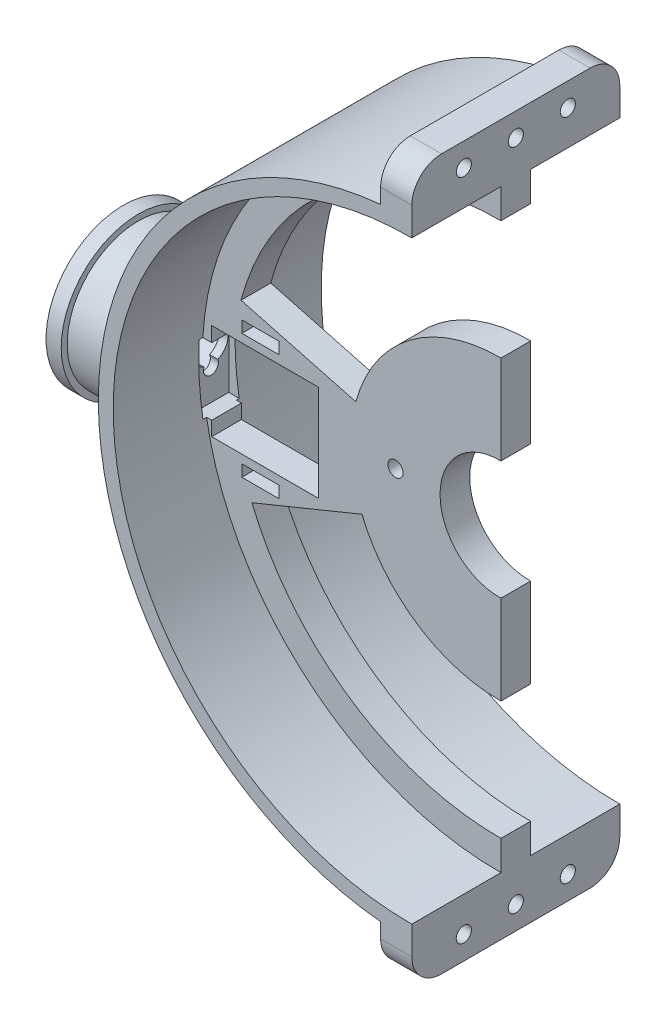
SolidWorks part; units mm, degrees
material "ABS"
ref_plane "前视" through (0, 0, 0) normal (0, 0, 1) x (1, 0, 0)
ref_plane "上视" through (0, 0, 0) normal (0, 1, 0) x (1, 0, 0)
ref_plane "右视" through (0, 0, 0) normal (1, 0, 0) x (0, 0, -1)
sketch "草图1" plane through (0, 0, 0) normal (0, 1, 0) x (1, 0, 0)
  line L0 (0, 10) -> (105, 10)
  line L1 (105, 0) -> (0, 0)
  line L2 (105, 10) -> (105, 0)
  line L7 (0, 0) -> (0, 10)
  point P5 (0, 5)
revolve "旋转1" add sketch "草图1" angle 360 about L7
sketch "草图11" plane through (0, 0, 0) normal (0, 0, 1) x (1, 0, 0)
  circle A3 centre (0, 0) radius 100
  circle A5 centre (0, 0) radius 105
  point P10 (-99.5455, -9.5238)
  point P11 (99.5455, -9.5238)
  dimension "D1" = 5
extrude "凸台-拉伸3" add sketch "草图11" along normal blind 10 and the other way blind 20
sketch "草图12" plane through (0, 0, 10) normal (0, 0, 1) x (1, 0, 0)
  circle A0 centre (0, 0) radius 105
  circle A1 centre (0, 0) radius 100
extrude "凸台-拉伸4" add sketch "草图12" along normal blind 20
ref_plane "基准面5" through (0, 0, -5) normal (0, 0, 1) x (1, 0, 0)
mirror "镜向1" about plane through (0, 0, -5) normal (0, 0, 1) of "凸台-拉伸4"
ref_plane "基准面1" through (100, 0, 0) normal (1, 0, 0) x (0, 0, -1)
sketch "草图4" plane through (100, 0, 0) normal (1, 0, 0) x (0, 0, -1)
  circle A0 centre (5, 0) radius 20.5
  circle A1 centre (5, 0) radius 25.5
  dimension "D1" = 41
  dimension "D2" = 5
extrude "凸台-拉伸6" add sketch "草图4" along normal blind 20
ref_plane "基准面2" through (-100, 0, 0) normal (1, 0, 0) x (0, 0, -1)
sketch "草图5" plane through (-100, 0, 0) normal (1, 0, 0) x (0, 0, -1)
  circle A0 centre (5, 0) radius 21
  circle A1 centre (5, 0) radius 26
  dimension "D1" = 5
  dimension "D2" = 42
extrude "凸台-拉伸7" add sketch "草图5" against normal blind 31.5984
sketch "草图6" plane through (0, 0, 0) normal (0, 0, 1) x (1, 0, 0)
  line L0 (0, 0) -> (50000, 0) construction
  circle A0 centre (0, -70) radius 20
  circle A1 centre (0, 70) radius 20
  dimension "D1" = 40
extrude "切除-拉伸1" cut sketch "草图6" against normal through all
ref_plane "基准面6" through (105, 0, 0) normal (1, 0, 0) x (0, 0, -1)
sketch "草图16" plane through (105, 0, 0) normal (1, 0, 0) x (0, 0, -1)
  arc A0 (7.3015, -5.3238) -> (2.6985, -5.3238) centre (5, 0) ccw
  arc A1 (2.6985, -5.3238) -> (7.3015, -5.3238) centre (5, -6.3) ccw
  dimension "D1" = 6.3
extrude "切除-拉伸8" cut sketch "草图16" against normal blind 10
sketch "草图17" plane through (100, 0, 0) normal (1, 0, 0) x (0, 0, -1)
  line L0 (-1.2095, -16.8) -> (-1.2095, 5.8)
  line L1 (-1.2095, -16.8) -> (10.9905, -16.8)
  line L2 (-1.2095, 5.8) -> (10.9905, 5.8)
  line L3 (10.9905, -16.8) -> (10.9905, 5.8)
  line L4 (-1.2095, -16.8) -> (10.9905, 5.8) construction
  line L5 (-1.2095, 5.8) -> (10.9905, -16.8) construction
  point P0 (4.8905, 5.8)
  point P1 (4.8905, -5.5)
  dimension "D1" = 12.2
  dimension "D2" = 22.6
extrude "切除-拉伸9" cut sketch "草图17" against normal blind 4.05 and the other way blind 2.1
sketch "草图19" plane through (95.95, 0, 0) normal (1, 0, 0) x (0, 0, -1)
  line L0 (-1.1226, -16.8) -> (-1.1226, 5.8)
  line L3 (11.0774, -16.8) -> (11.0774, 5.8)
  line L4 (-1.1226, -16.8) -> (11.0774, 5.8) construction
  line L5 (-1.1226, 5.8) -> (11.0774, -16.8) construction
  line L6 (5, 5.8) -> (50005, 5.8) construction
  line L8 (-1.1226, 5.8) -> (-1.1226, 10.8)
  line L9 (11.0774, 5.8) -> (11.0774, 10.8)
  line L10 (-1.1226, 10.8) -> (11.0774, 10.8)
  line L12 (-1.1226, -16.8) -> (-1.1226, -21.6)
  line L13 (11.0774, -16.8) -> (11.0774, -21.6)
  line L14 (-1.1226, -21.6) -> (11.0774, -21.6)
  arc A1 (7.3015, -5.3238) -> (2.6985, -5.3238) centre (5, 0) ccw construction
  point P7 (5, 5.8)
  dimension "D1" = 22.6
  dimension "D3" = 12.2
  dimension "D4" = 5
  dimension "D5" = 4.8
extrude "切除-拉伸10" cut sketch "草图19" against normal blind 35 and the other way blind 0.9
mirror "镜向2" about plane through (0, 0, 0) normal (1, 0, 0) of "切除-拉伸10", "切除-拉伸9", "切除-拉伸8"
sketch "草图21" plane through (0, 0, 0) normal (0, 0, 1) x (1, 0, 0)
  line L0 (0, -5.4) -> (-50000, -5.4) construction
  line L1 (-86.7142, 17.5498) -> (-74.2282, 17.5498)
  line L2 (-86.7142, 17.5498) -> (-86.7142, 13.6144)
  line L3 (-86.7142, 13.6144) -> (-74.2282, 13.6144)
  line L4 (-74.2282, 17.5498) -> (-74.2282, 13.6144)
  line L5 (-60.95, 10.8) -> (-60.95, -21.6) construction
  line L6 (-86.7142, -24.4144) -> (-74.2282, -24.4144)
  line L7 (-74.2282, -28.3498) -> (-74.2282, -24.4144)
  line L8 (-86.7142, -28.3498) -> (-74.2282, -28.3498)
  line L9 (-86.7142, -28.3498) -> (-86.7142, -24.4144)
  line L10 (0, 0) -> (0, -50000) construction
  line L11 (86.7142, -28.3498) -> (86.7142, -24.4144)
  line L12 (86.7142, -28.3498) -> (74.2282, -28.3498)
  line L13 (74.2282, -28.3498) -> (74.2282, -24.4144)
  line L14 (86.7142, -24.4144) -> (74.2282, -24.4144)
  line L15 (86.7142, 13.6144) -> (74.2282, 13.6144)
  line L16 (74.2282, 17.5498) -> (74.2282, 13.6144)
  line L17 (86.7142, 17.5498) -> (74.2282, 17.5498)
  line L18 (86.7142, 17.5498) -> (86.7142, 13.6144)
  point P9 (-60.95, -5.4)
extrude "切除-拉伸11" cut sketch "草图21" against normal through all
ref_plane "基准面7" through (0, 0, -5) normal (0, 0, 1) x (1, 0, 0)
sketch "草图23" plane through (0, 0, -5) normal (0, 0, 1) x (1, 0, 0)
  line L1 (120, -25.5) -> (120, 25.5) construction
  line L2 (105, 28) -> (105, 24)
  line L4 (105, 24) -> (126.5, 24)
  line L5 (126.5, 28) -> (126.5, 24)
  line L6 (105, 28) -> (126.5, 28)
  circle A0 centre (0, 0) radius 105 construction
  point P6 (110.9927, 25)
  dimension "D4" = 6.5
  dimension "D1" = 4
  dimension "D2" = 21.5
  dimension "D3" = 105
revolve "切除-旋转1" cut sketch "草图23" angle 360 about axis through (120, 0, -5) along (-1, 0, 0)
mirror "镜向3" about plane through (0, 0, 0) normal (1, 0, 0) of "切除-旋转1"
sketch "草图24" plane through (0, 0, 0) normal (0, 0, 1) x (1, 0, 0)
  line L0 (-86.9794, 23.121) -> (-48.3219, 12.845)
  line L1 (0, 0) -> (0, 50000) construction
  line L2 (46.2796, -18.9261) -> (83.3033, -34.067)
  line L3 (48.3219, 12.845) -> (86.9794, 23.121)
  circle A0 centre (0, 0) radius 20
  arc A2 (86.9794, 23.121) -> (-86.9794, 23.121) centre (0, 0) ccw
  arc A3 (83.3033, -34.067) -> (-83.3033, -34.067) centre (0, 0) cw
  arc A5 (48.3219, 12.845) -> (-48.3219, 12.845) centre (0, 0) ccw
  arc A6 (46.2796, -18.9261) -> (-46.2796, -18.9261) centre (0, 0) cw
  spline S0 degree 1 poles (-83.3033, -34.067) (-46.2796, -18.9261) knots 0 0 1 1
  dimension "D1" = 40
  dimension "D3" = 40
  dimension "D4" = 40
extrude "切除-拉伸12" cut sketch "草图24" against normal through all contours A0 | L3 A2 L0 A5 | L2 A3 S0 A6
sketch "草图25" plane through (0, 5.8, 0) normal (0, -1, 0) x (1, 0, 0)
  line L0 (102.1, -5) -> (102.1, 1.2095) construction
  line L1 (96.85, -10) -> (102.1, -10)
  line L2 (96.85, -10) -> (96.85, 0)
  line L3 (96.85, 0) -> (102.1, 0)
  line L4 (102.1, -10) -> (102.1, 0)
extrude "切除-拉伸13" cut sketch "草图25" against normal blind 1
sketch "草图26" plane through (0, 0, -5) normal (0, 0, 1) x (1, 0, 0)
  line L1 (0, 0) -> (0, 50000) construction
  line L3 (-10, 104.5227) -> (-10, 119.5227)
  line L4 (-10, 119.5227) -> (10, 119.5227)
  line L5 (10, 104.5227) -> (10, 119.5227)
  arc A0 (-10, 104.5227) -> (10, 104.5227) centre (0, 0) cw
  circle A1 centre (0, 0) radius 105 construction
  dimension "D1" = 20
  dimension "D2" = 15
extrude "凸台-拉伸8" add sketch "草图26" along normal blind 35 and the other way blind 35
fillet "圆角1" radius 10 2 edges at (0, 119.5227, -40) (0, 119.5227, 30)
mirror "镜向4" about plane through (0, 0, 0) normal (0, 1, 0) of "圆角1", "凸台-拉伸8"
hole_wizard "M5x0.8 螺纹孔1" positions "草图29" profile "草图28" tap size "M5x0.8" standard "ANSI Metric" end condition up to next
sketch "草图29" plane through (10, 0, 0) normal (1, 0, 0) x (0, 0, -1)
  line L0 (5, 110) -> (5, -110) construction
  line L1 (-30, 104.5227) -> (-30, 109.5227) construction
  point P0 (-12.5, 111.6754)
  point P2 (5, 111.6754)
  point P6 (22.5, 111.6754)
  point P11 (-30, 107.0227)
  dimension "D1" = 17.5
  dimension "D2" = 17.5
  dimension "D3" = 17.5
  dimension "D4" = 17.5
sketch "草图28" plane through (10, 111.6754, 12.5) normal (0, 1, 0) x (0, 0, -1)
  line L0 (0, 0) -> (0, 20.001)
  line L1 (0, 20.001) -> (2.1, 20.001)
  line L2 (2.1, 20.001) -> (2.1, 0)
  line L5 (2.1, 0) -> (0, 0)
  line L11 (0, -6.35) -> (0, 107.95) construction
  dimension "通孔螺纹孔钻头直径" = 4.2
  dimension "通孔螺纹孔钻头深度" = 20.001
cosmetic thread "孔螺蚊线1" parameters "D2"=5
cosmetic thread "孔螺蚊线2" parameters "D2"=5
cosmetic thread "孔螺蚊线3" parameters "D2"=5
sketch "草图38" plane through (10, 0, 0) normal (1, 0, 0) x (0, 0, -1)
  circle A0 centre (-12.5, 111.6754) radius 2.55
  circle A1 centre (5, 111.6754) radius 2.55
  circle A2 centre (22.5, 111.6754) radius 2.55
  dimension "D1" = 5.1
  dimension "D2" = 5.1
  dimension "D3" = 5.1
extrude "切除-拉伸17" cut sketch "草图38" against normal through all
mirror "镜向5" about plane through (0, 0, 0) normal (0, 1, 0) of "切除-拉伸17", "M5x0.8 螺纹孔1"
hole_wizard "M5x0.8 螺纹孔2" positions "草图31" profile "草图32" tap size "M5x0.8" standard "ANSI Metric" end condition up to next
sketch "草图31" plane through (0, 0, 0) normal (0, 0, 1) x (1, 0, 0)
  point P0 (-35, 0)
  point P2 (35, 0)
  dimension "D1" = 35
  dimension "D2" = 35
sketch "草图32" plane through (-35, 0, 0) normal (1, 0, 0) x (0, -1, 0)
  line L0 (0, 0) -> (0, 10)
  line L1 (0, 10) -> (2.1, 10)
  line L2 (2.1, 10) -> (2.1, 0)
  line L5 (2.1, 0) -> (0, 0)
  line L11 (0, -6.35) -> (0, 107.95) construction
  dimension "通孔螺纹孔钻头直径" = 4.2
  dimension "通孔螺纹孔钻头深度" = 10
cosmetic thread "孔螺蚊线4" parameters "D1"=10, "D2"=5
cosmetic thread "孔螺蚊线5" parameters "D1"=10, "D2"=5
sketch "草图39" plane through (0, 0, 0) normal (0, 0, 1) x (1, 0, 0)
  circle A0 centre (-35, 0) radius 2.55
  circle A1 centre (35, 0) radius 2.55
  dimension "D1" = 5.1
  dimension "D2" = 5.1
extrude "切除-拉伸18" cut sketch "草图39" against normal through all and the other way through all
sketch "草图33" plane through (0, 0, 0) normal (0, 0, 1) x (1, 0, 0)
  line L0 (-18.2158, -32) -> (49981.7842, -32) construction
  line L2 (-31.5, -32) -> (31.5, -32)
  line L4 (-31.5, -26.8391) -> (31.5, -26.8391)
  arc A4 (-31.5, -26.8391) -> (-31.5, -32) centre (-31.5, -29.4196) ccw
  arc A5 (31.5, -26.8391) -> (31.5, -32) centre (31.5, -29.4196) cw
  dimension "D1" = 32
extrude "凸台-拉伸9" [suppressed] add sketch "草图33" along normal blind 5
sketch "草图34" plane through (0, 0, 0) normal (0, 0, 1) x (1, 0, 0)
  line L1 (0.5, -147.4639) -> (209.1586, -147.4639)
  line L2 (0.5, -147.4639) -> (0.5, 128.7315)
  line L3 (0.5, 128.7315) -> (209.1586, 128.7315)
  line L4 (209.1586, -147.4639) -> (209.1586, 128.7315)
  dimension "D1" = 0.5
extrude "切除-拉伸14" cut sketch "草图34" against normal through all and the other way through all
sketch "草图35" plane through (0, 0, 0) normal (0, 0, 1) x (1, 0, 0)
  circle A0 centre (0, 0) radius 90
extrude "切除-拉伸15" [suppressed] cut sketch "草图35" against normal through all
sketch "草图37" plane through (0, 0, 30) normal (0, 0, 1) x (1, 0, 0)
  line L0 (-121.0876, 43.0386) -> (-98.8783, 35.3282)
  line L1 (-121.1107, -42.9735) -> (-97.6082, -38.6994)
  arc A0 (-98.8783, 35.3282) -> (-97.6082, -38.6994) centre (0, 0) ccw
  arc A1 (-10, 104.5227) -> (-10, -104.5227) centre (0, 0) ccw construction
  arc A2 (-121.0876, 43.0386) -> (-121.1107, -42.9735) centre (0, 0) ccw
extrude "切除-拉伸16" [suppressed] cut sketch "草图37" against normal through all
sketch "草图40" plane through (0, 0, -40) normal (0, 0, -1) x (-1, 0, 0)
  line L1 (-99.5458, 143.5348) -> (165.1608, 143.5348)
  line L2 (-99.5458, 143.5348) -> (-99.5458, -145.5532)
  line L3 (-99.5458, -145.5532) -> (165.1608, -145.5532)
  line L4 (165.1608, 143.5348) -> (165.1608, -145.5532)
extrude "切除-拉伸19" [suppressed] cut sketch "草图40" against normal blind 30
equation "\"10、\"=10.5049"
